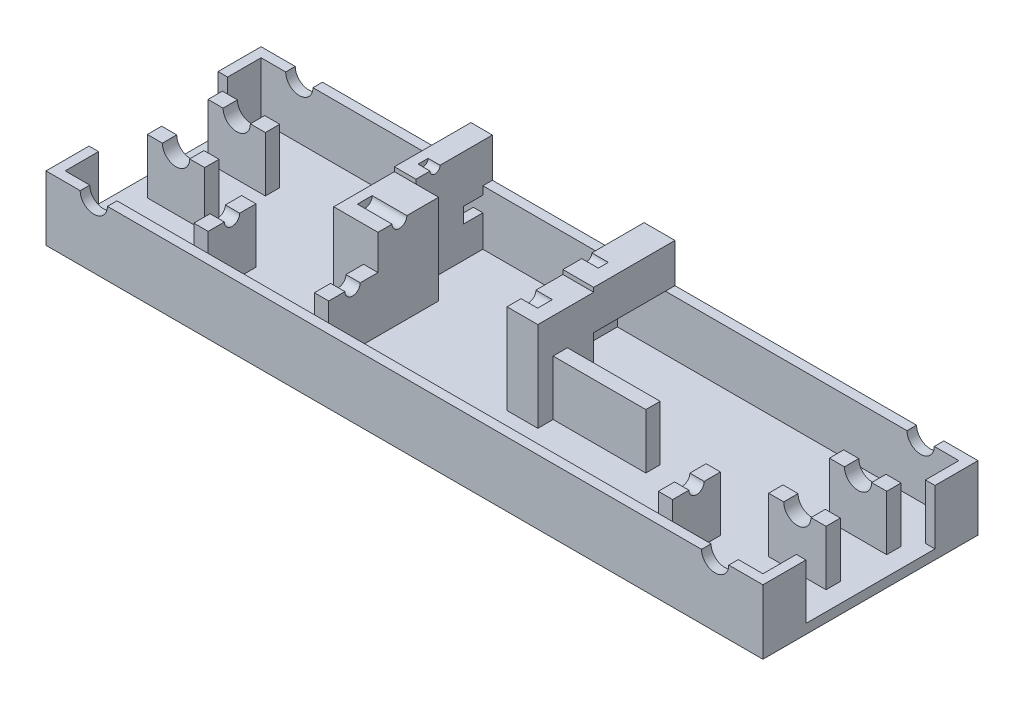
SolidWorks part; units mm, degrees
ref_plane "前视基准面" through (0, 0, 0) normal (0, 0, 1) x (1, 0, 0)
ref_plane "上视基准面" through (0, 0, 0) normal (0, 1, 0) x (1, 0, 0)
ref_plane "右视基准面" through (0, 0, 0) normal (1, 0, 0) x (0, 0, -1)
other "Configuration Table"
sketch "草图1" plane through (0, 0, 0) normal (0, 1, 0) x (1, 0, 0)
  line L1 (-75, -22.5) -> (75, -22.5)
  line L2 (-75, -22.5) -> (-75, 22.5)
  line L3 (-75, 22.5) -> (75, 22.5)
  line L4 (75, -22.5) -> (75, 22.5)
  line L5 (-75, -22.5) -> (75, 22.5) construction
  line L6 (-75, 22.5) -> (75, -22.5) construction
  point P0 (0, 0)
  dimension "D1" = 150
  dimension "D2" = 45
extrude "凸台-拉伸1" add sketch "草图1" along normal blind 2
sketch "草图2" plane through (0, 2, 0) normal (0, 1, 0) x (1, 0, 0)
  line L0 (-75, 22.5) -> (75, 22.5)
  line L1 (75, 22.5) -> (75, 13.5)
  line L2 (75, -22.5) -> (75, 22.5) construction
  line L3 (75, -22.5) -> (-75, -22.5)
  line L4 (-75, -22.5) -> (-75, -13.5)
  line L5 (-73, 20.5) -> (-28.6, 20.5)
  line L6 (73, 20.5) -> (73, 13.5)
  line L7 (73, -20.5) -> (-73, -20.5)
  line L8 (-73, -20.5) -> (-73, -13.5)
  line L9 (1.55, 20.5) -> (73, 20.5)
  line L23 (-0.95, 20.5) -> (-0.95, 8.5)
  line L24 (-73, 13.5) -> (-75, 13.5)
  line L25 (-75, -13.5) -> (-73, -13.5)
  line L26 (75, 13.5) -> (73, 13.5)
  line L27 (75, -13.5) -> (73, -13.5)
  line L28 (-75, 13.5) -> (-75, 22.5)
  line L29 (-73, 13.5) -> (-73, 20.5)
  line L30 (73, -13.5) -> (73, -20.5)
  line L31 (75, -13.5) -> (75, -22.5)
  line L32 (-0.95, 8.5) -> (1.55, 8.5)
  line L33 (-71, -2.3) -> (-59, -2.3)
  line L34 (-71, -2.3) -> (-71, -5.3)
  line L35 (-71, -5.3) -> (-59, -5.3)
  line L36 (-59, -2.3) -> (-59, -5.3)
  line L37 (-75, 22.5) -> (-75, -22.5) construction
  line L38 (59, -2.3) -> (71, -2.3)
  line L39 (59, -2.3) -> (59, -5.3)
  line L40 (59, -5.3) -> (71, -5.3)
  line L41 (71, -2.3) -> (71, -5.3)
  line L42 (75, -22.5) -> (75, 22.5) construction
  line L43 (-55, -5.4) -> (-75, -5.4) construction
  line L44 (75, -5.4) -> (55, -5.4) construction
  line L45 (66.4142, 10.5) -> (67.4958, 10.5) construction
  line L46 (-71, 10.4) -> (-59, 10.4)
  line L47 (-71, 10.4) -> (-71, 7.4)
  line L48 (-71, 7.4) -> (-59, 7.4)
  line L49 (-59, 10.4) -> (-59, 7.4)
  line L50 (59, 10.4) -> (71, 10.4)
  line L51 (59, 10.4) -> (59, 7.4)
  line L52 (59, 7.4) -> (71, 7.4)
  line L53 (71, 10.4) -> (71, 7.4)
  line L54 (-63.5858, 10.5) -> (-62.5042, 10.5) construction
  line L55 (1.55, 20.5) -> (1.55, 8.5)
  line L57 (-28.6, 20.5) -> (-28.6, 6.5)
  line L58 (-28.6, 6.5) -> (-26.6, 6.5)
  line L59 (-26.6, 20.5) -> (-26.6, 6.5)
  line L60 (-26.6, 20.5) -> (-0.95, 20.5)
  point P57 (-26.6, 13.5)
  dimension "D1" = 2
  dimension "D2" = 2
  dimension "D3" = 2
  dimension "D4" = 2
  dimension "D5" = 9
  dimension "D6" = 3
  dimension "D7" = 3
  dimension "D8" = 12
  dimension "D9" = 12
  dimension "D10" = 4
  dimension "D11" = 4
  dimension "D12" = 0.1
  dimension "D13" = 0.1
  dimension "D14" = 0.1
  dimension "D15" = 0.1
  dimension "D16" = 3
  dimension "D17" = 2.5
  dimension "D18" = 2
  dimension "D19" = 71.45
  dimension "D20" = 12
  dimension "D21" = 48.4
  dimension "D22" = 14
extrude "凸台-拉伸2" add sketch "草图2" along normal up to surface (11.5 mm away)
sketch "草图4" plane through (0, 2, 0) normal (0, 1, 0) x (1, 0, 0)
  line L0 (1.55, 20.5) -> (73, 20.5) construction
  line L1 (-50.0747, -6.5) -> (-47.0747, -6.5)
  line L2 (-50.0747, -6.5) -> (-50.0747, -16.5)
  line L3 (-50.0747, -16.5) -> (-47.0747, -16.5)
  line L4 (-47.0747, -6.5) -> (-47.0747, -16.5)
  line L5 (-31.1, 6.5) -> (-21.85, 6.5)
  line L6 (-31.1, 6.5) -> (-31.1, -6.2)
  line L7 (-24.85, -16.5) -> (-21.85, -16.5)
  line L8 (-21.85, 6.5) -> (-21.85, -16.5)
  line L9 (47.1147, -6.5) -> (50.1147, -6.5)
  line L10 (47.1147, -6.5) -> (47.1147, -16.5)
  line L11 (47.1147, -16.5) -> (50.1147, -16.5)
  line L12 (50.1147, -6.5) -> (50.1147, -16.5)
  line L13 (5.15, 5.5) -> (11.6, 5.5)
  line L14 (5.15, 5.5) -> (5.15, -6.2)
  line L15 (5.15, -6.2) -> (11.6, -6.2)
  line L16 (11.6, 5.5) -> (11.6, 0)
  line L26 (31, 0) -> (11.6, 0)
  line L28 (11.6, -3) -> (31, -3)
  line L31 (-50.2747, -15.25) -> (-50.2747, -7.75) construction
  line L32 (50.3147, -7.75) -> (50.3147, -15.25) construction
  line L33 (-29.7348, -10) -> (-29.7348, -13) construction
  line L34 (56.24, -10) -> (-56.2, -10) construction
  line L35 (-56.2, -13) -> (56.24, -13) construction
  line L36 (-29.7348, -11.5) -> (-37.5732, -11.5) construction
  line L37 (-21.55, -10.8234) -> (-21.55, -11.245) construction
  line L38 (31, 0) -> (31, -3)
  line L40 (11.6, -3) -> (11.6, -6.2)
  line L41 (75, -13.5) -> (75, 13.5) construction
  line L42 (-26.35, -3.2) -> (7.05, -3.2) construction
  line L43 (-31.1, -6.2) -> (-24.85, -6.2)
  line L44 (-24.85, -6.2) -> (-24.85, -16.5)
  line L45 (11.7, 3.8856) -> (11.7, 17.1144) construction
  line L46 (5.05, 2.196) -> (5.05, 3.4405) construction
  line L47 (-75, 13.5) -> (-75, -13.5) construction
  line L48 (-73, 20.5) -> (-28.6, 20.5) construction
  point P47 (8.375, 5.5)
  dimension "D1" = 3
  dimension "D2" = 43.9
  dimension "D3" = 3
  dimension "D4" = 10
  dimension "D5" = 0.2
  dimension "D6" = 0.2
  dimension "D7" = 0.3
  dimension "D8" = 14
  dimension "D9" = 44
  dimension "D10" = 3
  dimension "D11" = 3
  dimension "D12" = 0.1
  dimension "D13" = 3
  dimension "D14" = 0.1
  dimension "D15" = 15
extrude "凸台-拉伸3" add sketch "草图4" along normal up to surface (11.5 mm away) up to face at (-6.825, 13.5, -15.75)
sketch "草图5" plane through (0, 0, 22.5) normal (0, 0, 1) x (1, 0, 0)
  circle A0 centre (-65, 13.5) radius 2.85
  arc A1 (-63.05, 11.5609) -> (-63.05, 15.4391) centre (-65, 13.5) ccw construction
  circle A2 centre (65, 13.5) radius 2.85
  arc A3 (66.95, 11.5609) -> (66.95, 15.4391) centre (65, 13.5) ccw construction
  dimension "D1" = 0.1
  dimension "D2" = 0.1
extrude "切除-拉伸1" cut sketch "草图5" against normal up to surface (45 mm away) up to face at (0, 6.75, -22.5)
sketch "草图6" plane through (50.1147, 0, 0) normal (1, 0, 0) x (0, 0, -1)
  line L0 (-16.5, 13.5) -> (-6.5, 13.5) construction
  circle A0 centre (-11.5, 13.5) radius 1.6
  circle A1 centre (-11.5, 13.5) radius 1.5 construction
  dimension "D1" = 0.1
extrude "切除-拉伸2" cut sketch "草图6" against normal up to surface (125.1147 mm away) up to face at (-75, 7.25, 0)
sketch "草图7" plane through (0, 13.5, 0) normal (0, 1, 0) x (1, 0, 0)
  line L0 (5.15, 22.5) -> (5.15, -6.2)
  line L3 (5.15, 22.5) -> (11.6, 22.5)
  line L4 (11.6, -6.2) -> (11.6, 22.5)
  line L5 (-26.6, 22.5) -> (-26.6, 6.5)
  line L6 (-26.6, 6.5) -> (-21.85, 6.5)
  line L7 (-21.85, 6.5) -> (-21.85, -6.2)
  line L8 (-21.85, -9.9) -> (-21.85, 6.5) construction
  line L9 (-21.85, -6.2) -> (-31.1, -6.2)
  line L10 (-31.1, -6.2) -> (-31.1, 22.5)
  line L11 (-31.1, 22.5) -> (-26.6, 22.5)
  line L12 (-21.85, 6.5) -> (-26.6, 6.5) construction
  line L13 (62.15, 22.5) -> (-62.15, 22.5) construction
  line L14 (5.15, -6.2) -> (11.6, -6.2)
  line L15 (-75, 22.5) -> (-75, 13.5) construction
  line L17 (11.6, -6.2) -> (11.6, -3) construction
  dimension "D2" = 48.4
  dimension "D3" = 4.5
extrude "凸台-拉伸6" add sketch "草图7" along normal up to surface (7.3 mm away)
sketch "草图8" plane through (0, 20.8, 0) normal (0, 1, 0) x (1, 0, 0)
  line L1 (-31.1, 22.5) -> (-26.6, 22.5)
  line L2 (-31.1, 22.5) -> (-31.1, 6.5)
  line L3 (-31.1, 6.5) -> (-26.6, 6.5)
  line L4 (-26.6, 22.5) -> (-26.6, 6.5)
  line L5 (5.15, 22.5) -> (11.6, 22.5)
  line L6 (5.15, 22.5) -> (5.15, 5.5)
  line L7 (5.15, 5.5) -> (11.6, 5.5)
  line L8 (11.6, 22.5) -> (11.6, 5.5)
extrude "凸台-拉伸7" add sketch "草图8" along normal up to surface (0.9 mm away)
sketch "草图9" plane through (11.6, 0, 0) normal (1, 0, 0) x (0, 0, -1)
  circle A0 centre (10.5, 21.7) radius 1.05
  circle A1 centre (-1.7, 20.8) radius 1.55
  circle A2 centre (10.5, 21.7) radius 1 construction
  circle A3 centre (-1.7, 20.8) radius 1.5 construction
  dimension "D1" = 0.05
  dimension "D2" = 0.05
extrude "切除-拉伸3" cut sketch "草图9" against normal offset from surface (37.7 mm away) 2 from offset 3 up to face at (-31.1, 14.3889, -8.7889) offset against normal yes
sketch "草图10" plane through (1.55, 0, 0) normal (1, 0, 0) x (0, 0, -1)
  line L0 (20.5, 13.5) -> (20.5, 2) construction
  line L1 (16.5, 11.8) -> (20.5, 11.8)
  line L2 (16.5, 11.8) -> (16.5, 8.6)
  line L3 (16.5, 8.6) -> (20.5, 8.6)
  line L4 (20.5, 11.8) -> (20.5, 8.6)
  line L5 (16.6, 8.7) -> (20.4, 8.7) construction
  line L9 (16.6, 11.7) -> (20.4, 11.7) construction
  line L10 (16.6, 11.7) -> (16.6, 8.7) construction
  dimension "D1" = 0.1
  dimension "D2" = 0.1
  dimension "D3" = 0.1
extrude "切除-拉伸4" cut sketch "草图10" against normal up to surface (30.15 mm away) up to face at (-28.6, 7.75, -13.5)
